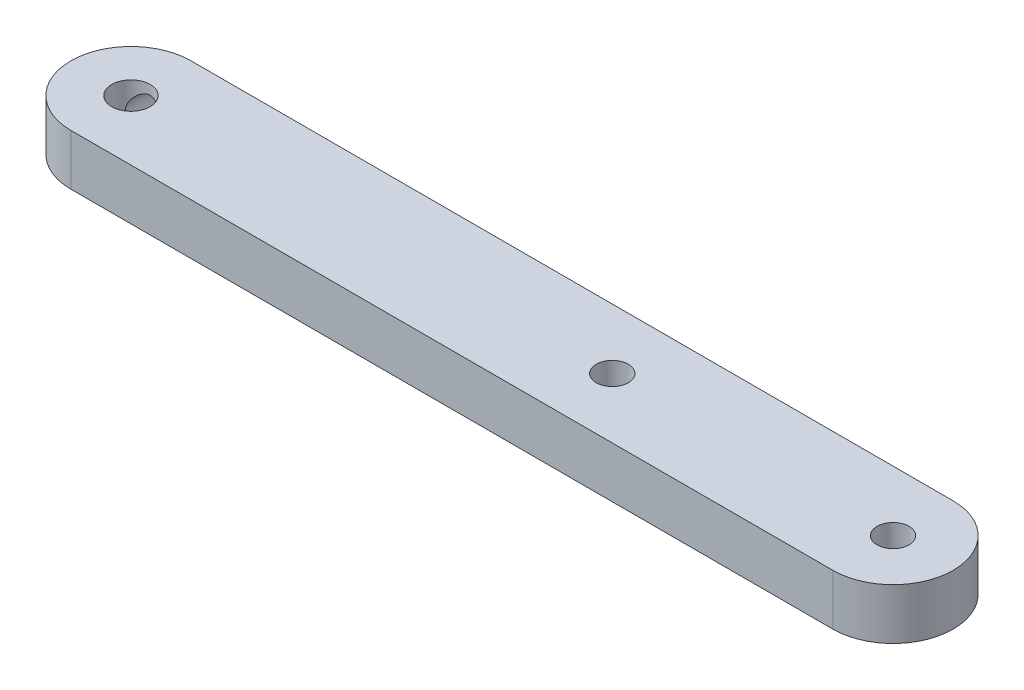
SolidWorks part; units mm, degrees
ref_plane "Front Plane" through (0, 0, 0) normal (0, 0, 1) x (1, 0, 0)
ref_plane "Top Plane" through (0, 0, 0) normal (0, 1, 0) x (1, 0, 0)
ref_plane "Right Plane" through (0, 0, 0) normal (1, 0, 0) x (0, 0, -1)
sketch "Sketch1" plane through (0, 0, 0) normal (0, 1, 0) x (1, 0, 0)
  line L7 (0, 0) -> (95, 0) construction
  line L8 (0, 7.5) -> (95, 7.5)
  line L9 (0, -7.5) -> (95, -7.5)
  circle A1 centre (0, 0) radius 2.4
  arc A2 (0, -7.5) -> (0, 7.5) centre (0, 0) ccw construction
  circle A5 centre (0, 0) radius 11.725 construction
  arc A8 (0, 7.5) -> (0, -7.5) centre (0, 0) ccw
  arc A9 (95, -7.5) -> (95, 7.5) centre (95, 0) ccw
  circle A10 centre (60, 0) radius 2
  circle A11 centre (95, 0) radius 2
  point P17 (47.5, 0)
  dimension "D1" = 4.8
  dimension "D2" = 15
  dimension "D5" = 35
  dimension "D9" = 23.45
  dimension "D3" = 4
  dimension "D4" = 95
extrude "Boss-Extrude1" add sketch "Sketch1" along normal blind 6.35
sketch "Sketch2" plane through (0, 0, 0) normal (0, 0, 1) x (1, 0, 0)
  line L0 (0, 0) -> (0, 3.175) construction
  line L1 (0, 6.35) -> (0, 0) construction
  line L2 (0, 3.175) -> (-7.5, 3.175) construction
  line L3 (-7.5, 6.35) -> (-7.5, 0) construction
  circle A0 centre (0, 3.175) radius 2
  dimension "D1" = 4
extrude "Cut-Extrude1" cut sketch "Sketch2" against normal blind 10
